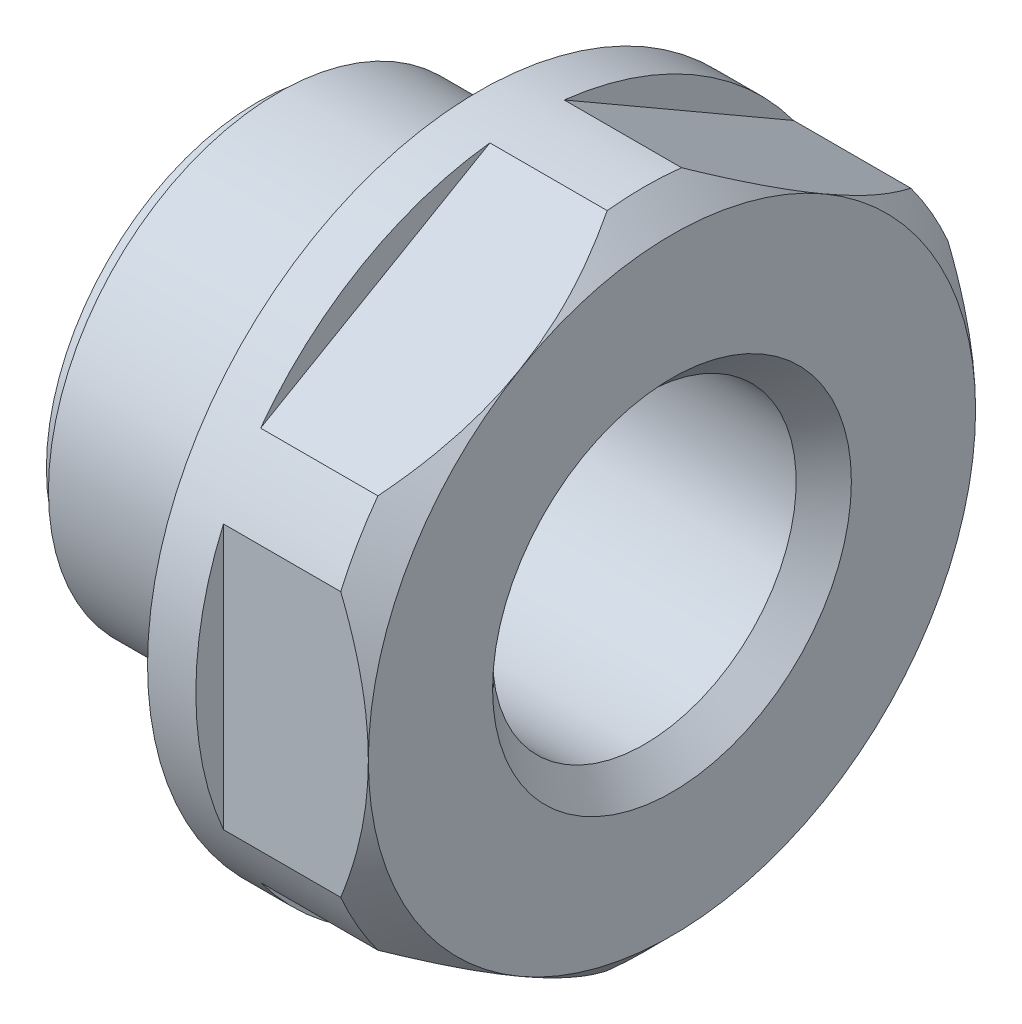
SolidWorks part; units mm, degrees
ref_plane "Piano frontale" through (0, 0, 0) normal (0, 0, 1) x (1, 0, 0)
ref_plane "Piano superiore" through (0, 0, 0) normal (0, 1, 0) x (1, 0, 0)
ref_plane "Piano destro" through (0, 0, 0) normal (1, 0, 0) x (0, 0, -1)
ref_plane "Piano1" through (0, 0, 0) normal (0, 0, 1) x (1, 0, 0)
sketch "Schizzo1" plane through (0, 0, 0) normal (0, 0, 1) x (1, 0, 0)
  line L0 (0, 6.5) -> (6.1538, 6.5)
  line L1 (6.1538, 6.5) -> (6.1538, 5.5)
  line L2 (6.1538, 5.5) -> (14, 5.5)
  line L3 (14, 5.5) -> (15, 6.5)
  line L4 (15, 6.5) -> (15, 11)
  line L5 (15, 11) -> (14, 12)
  line L6 (14, 12) -> (8, 12)
  line L7 (8, 12) -> (8, 8.33)
  line L8 (8, 8.33) -> (0.7404, 8.33)
  line L9 (0.7404, 8.33) -> (0.7404, 7.6636)
  line L10 (0.7404, 7.6636) -> (0, 7.6636)
  line L11 (0, 7.6636) -> (0, 6.5)
  line L12 (15, 0) -> (0, 0) construction
revolve "Rivoluzione1" add sketch "Schizzo1" angle 360 about L12 reverse direction yes
ref_plane "Piano2" through (15, 0, 0) normal (1, 0, 0) x (0, 0, -1)
sketch "Schizzo2" plane through (15, 0, 0) normal (1, 0, 0) x (0, 0, -1)
  line L0 (-16.5, -9.5263) -> (1, -19.6299)
  line L1 (1, -19.6299) -> (1, -13.2791)
  line L2 (1, -13.2791) -> (-11, -6.3509)
  line L3 (-11, -6.3509) -> (-11, 6.3509)
  line L4 (-11, 6.3509) -> (1, 13.2791)
  line L5 (1, 13.2791) -> (1, 19.6299)
  line L6 (1, 19.6299) -> (-16.5, 9.5263)
  line L7 (-16.5, 9.5263) -> (-16.5, -9.5263)
extrude "Taglio-Estrusione1" cut sketch "Schizzo2" against normal blind 5.25 and the other way blind 5.25
ref_plane "Piano3" through (15, 0, 0) normal (1, 0, 0) x (0, 0, -1)
sketch "Schizzo3" plane through (15, 0, 0) normal (1, 0, 0) x (0, 0, -1)
  line L0 (-1, -19.6299) -> (16.5, -9.5263)
  line L1 (16.5, -9.5263) -> (16.5, 9.5263)
  line L2 (16.5, 9.5263) -> (-1, 19.6299)
  line L3 (-1, 19.6299) -> (-1, 13.2791)
  line L4 (-1, 13.2791) -> (11, 6.3509)
  line L5 (11, 6.3509) -> (11, -6.3509)
  line L6 (11, -6.3509) -> (-1, -13.2791)
  line L7 (-1, -13.2791) -> (-1, -19.6299)
extrude "Taglio-Estrusione2" cut sketch "Schizzo3" against normal blind 5.25 and the other way blind 5.25
